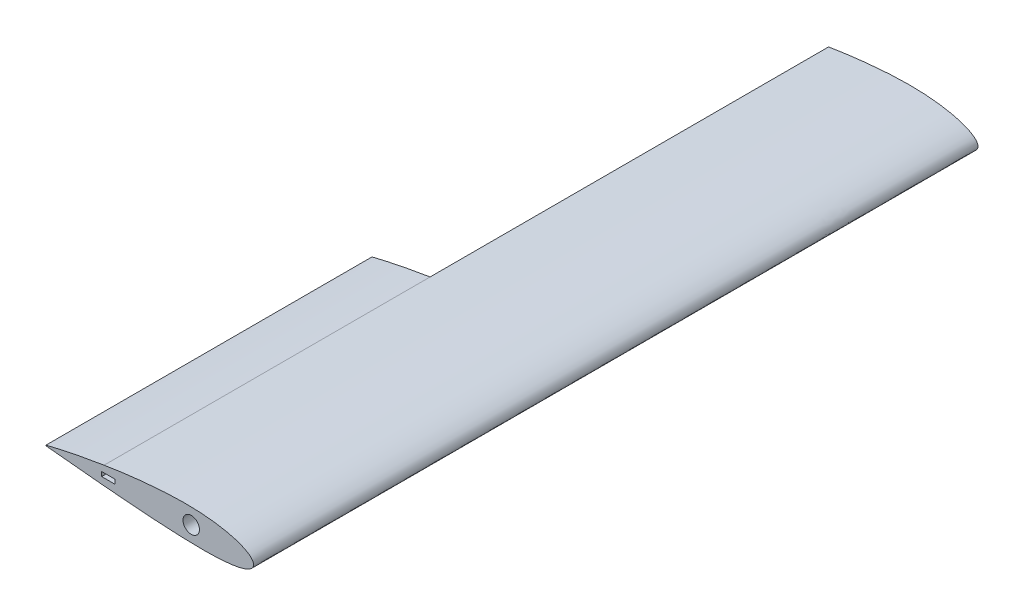
SolidWorks part; units mm, degrees
ref_plane "Front Plane" through (0, 0, 0) normal (0, 0, 1) x (1, 0, 0)
ref_plane "Top Plane" through (0, 0, 0) normal (0, 1, 0) x (1, 0, 0)
ref_plane "Right Plane" through (0, 0, 0) normal (1, 0, 0) x (0, 0, -1)
sketch "Sketch1" plane through (0, 0, 0) normal (0, 0, 1) x (1, 0, 0)
  line L0 (-230.9508, 18.5497) -> (-230.9508, -9.2543)
  spline S0 degree 3 poles (-230.9508, 18.5497) (-228.0495, 19.0122) (-221.2098, 20.1026) (-210.3095, 21.6942) (-198.1779, 23.3448) (-185.8013, 24.8762) (-173.2571, 26.268) (-160.6234, 27.4938) (-147.9795, 28.5305) (-135.3868, 29.3552) (-122.9015, 29.954) (-110.6006, 30.2332) (-98.5845, 30.1902) (-86.9568, 29.8182) (-75.7955, 29.1202) (-65.1756, 28.1047) (-55.1679, 26.7866) (-45.8384, 25.1864) (-37.2478, 23.33) (-29.4501, 21.2475) (-22.4931, 18.9719) (-16.4165, 16.538) (-11.2521, 13.9799) (-7.0224, 11.3279) (-3.7404, 8.6033) (-1.4142, 5.8093) (-0.0761, 2.9197) (0.1745, -0.0175) (-0.652, -2.8446) (-2.5184, -5.4132) (-5.3109, -7.7062) (-8.996, -9.7668) (-13.5586, -11.608) (-18.9775, -13.2303) (-25.2232, -14.6295) (-32.2591, -15.8018) (-40.0436, -16.7457) (-48.5308, -17.4629) (-57.6714, -17.959) (-67.413, -18.2439) (-77.7005, -18.3313) (-88.4762, -18.239) (-99.68, -17.9876) (-111.2496, -17.6014) (-123.1434, -17.1021) (-135.3121, -16.5233) (-147.6809, -15.8131) (-160.1528, -15.0012) (-172.6345, -14.109) (-185.0506, -13.1575) (-197.3255, -12.1663) (-209.3839, -11.1517) (-220.5687, -10.1827) (-227.7247, -9.5428) (-230.9508, -9.2543) knots 0 0 0 0 0.018424 0.043434 0.06908 0.095203 0.12164 0.148227 0.1748 0.201195 0.227364 0.253182 0.278347 0.30271 0.326128 0.348467 0.3696 0.389416 0.407811 0.424699 0.440008 0.453688 0.465715 0.476104 0.484928 0.49236 0.49873 0.504587 0.510443 0.516804 0.524199 0.532941 0.543186 0.554996 0.568376 0.583299 0.599709 0.617539 0.636704 0.657109 0.678651 0.701217 0.724685 0.748928 0.773811 0.799338 0.825326 0.851504 0.877716 0.9038 0.929596 0.954944 0.979688 1 1 1 1
extrude "Boss-Extrude1" add sketch "Sketch1" against normal blind 1120
sketch "Sketch2" plane through (0, 0, 0) normal (0, 0, 1) x (1, 0, 0)
  line L0 (-230.9508, 18.5497) -> (-230.9508, -9.2543)
  line L1 (-320.765, 0.5123) -> (-320.765, -0.5041)
  spline S0 degree 3 poles (-230.9508, 18.5497) (-231.8637, 18.4067) (-236.4436, 17.6893) (-244.5027, 16.319) (-254.9355, 14.4789) (-264.7762, 12.6466) (-273.9673, 10.8588) (-282.4535, 9.1392) (-290.1848, 7.5144) (-297.1155, 6.0094) (-303.2051, 4.6483) (-308.4182, 3.4537) (-312.7248, 2.4459) (-316.1, 1.6425) (-318.5247, 1.0579) (-319.9739, 0.7056) (-320.6133, 0.5494) (-320.765, 0.5123) knots 0 0 0 0 0.030252 0.151774 0.267626 0.37709 0.479485 0.574175 0.66057 0.73813 0.806369 0.864859 0.913229 0.951173 0.978451 0.994887 1 1 1 1
  spline S1 degree 3 poles (-230.9508, -9.2543) (-231.5339, -9.2025) (-235.782, -8.8249) (-243.5255, -8.1161) (-253.992, -7.1477) (-263.889, -6.2144) (-273.1542, -5.3269) (-281.7285, -4.4926) (-289.557, -3.719) (-296.5894, -3.0139) (-302.7801, -2.3837) (-308.0889, -1.8378) (-312.4807, -1.376) (-315.9277, -1.0227) (-318.4047, -0.7374) (-319.9003, -0.617) (-320.5749, -0.5034) (-320.7538, -0.504) (-320.765, -0.5041) knots 0 0 0 0 0.019463 0.141781 0.258505 0.3689 0.472262 0.567931 0.655294 0.733785 0.802892 0.862162 0.911205 0.949694 0.977373 0.994054 0.999628 1 1 1 1
extrude "Boss-Extrude2" add sketch "Sketch2" against normal blind 504
sketch "Sketch3" plane through (0, 0, 0) normal (0, 0, 1) x (1, 0, 0)
  circle A0 centre (-96.23, 6.014) radius 12.7
extrude "Cut-Extrude1" cut sketch "Sketch3" against normal blind 801
ref_plane "Plane1" through (0, 0, -376.7) normal (0, 0, 1) x (1, 0, 0)
sketch "Sketch4" plane through (0, 0, -376.7) normal (0, 0, 1) x (1, 0, 0)
  line L0 (-112.23, -19.05) -> (-80.23, -19.05)
  line L1 (-80.23, -19.05) -> (-80.23, 21.714)
  line L2 (-80.23, 21.714) -> (-112.23, 21.714)
  line L3 (-112.23, 21.714) -> (-112.23, -19.05)
extrude "Cut-Extrude2" cut sketch "Sketch4" along normal blind 46
ref_plane "Plane2" through (0, 0, -376.7) normal (0, 0, 1) x (1, 0, 0)
sketch "Sketch5" plane through (0, 0, -376.7) normal (0, 0, 1) x (1, 0, 0)
  line L0 (-286.612, -8.954) -> (-226.612, -8.954)
  line L1 (-226.612, -8.954) -> (-226.612, 3.046)
  line L2 (-226.612, 3.046) -> (-286.612, 3.046)
  line L3 (-286.612, 3.046) -> (-286.612, -8.954)
extrude "Cut-Extrude3" cut sketch "Sketch5" along normal blind 46
ref_plane "Plane3" through (0, 0, -598.5) normal (0, 0, 1) x (1, 0, 0)
sketch "Sketch6" plane through (0, 0, -598.5) normal (0, 0, 1) x (1, 0, 0)
  line L0 (-203.421, -16.843) -> (-149.421, -16.843)
  line L1 (-149.421, -16.843) -> (-149.421, 12.257)
  line L2 (-149.421, 12.257) -> (-203.421, 12.257)
  line L3 (-203.421, 12.257) -> (-203.421, -16.843)
extrude "Cut-Extrude4" cut sketch "Sketch6" along normal blind 64
ref_plane "Plane4" through (0, 0, -25.5) normal (0, 0, 1) x (1, 0, 0)
sketch "Sketch7" plane through (0, 0, -25.5) normal (0, 0, 1) x (1, 0, 0)
  line L0 (-234.736, 1.411) -> (-214.336, 1.411)
  line L1 (-214.336, 1.411) -> (-214.336, 8.211)
  line L2 (-214.336, 8.211) -> (-234.736, 8.211)
  line L3 (-234.736, 8.211) -> (-234.736, 1.411)
extrude "Cut-Extrude5" cut sketch "Sketch7" along normal blind 26
ref_plane "Plane5" through (0, 0, -930) normal (0, 0, 1) x (1, 0, 0)
sketch "Sketch8" plane through (0, 0, -930) normal (0, 0, 1) x (1, 0, 0)
  line L0 (-60, -19.254) -> (-40, -19.254)
  line L1 (-40, -19.254) -> (-40, -15.254)
  line L2 (-40, -15.254) -> (-60, -15.254)
  line L3 (-60, -15.254) -> (-60, -19.254)
extrude "Cut-Extrude6" cut sketch "Sketch8" along normal blind 20
